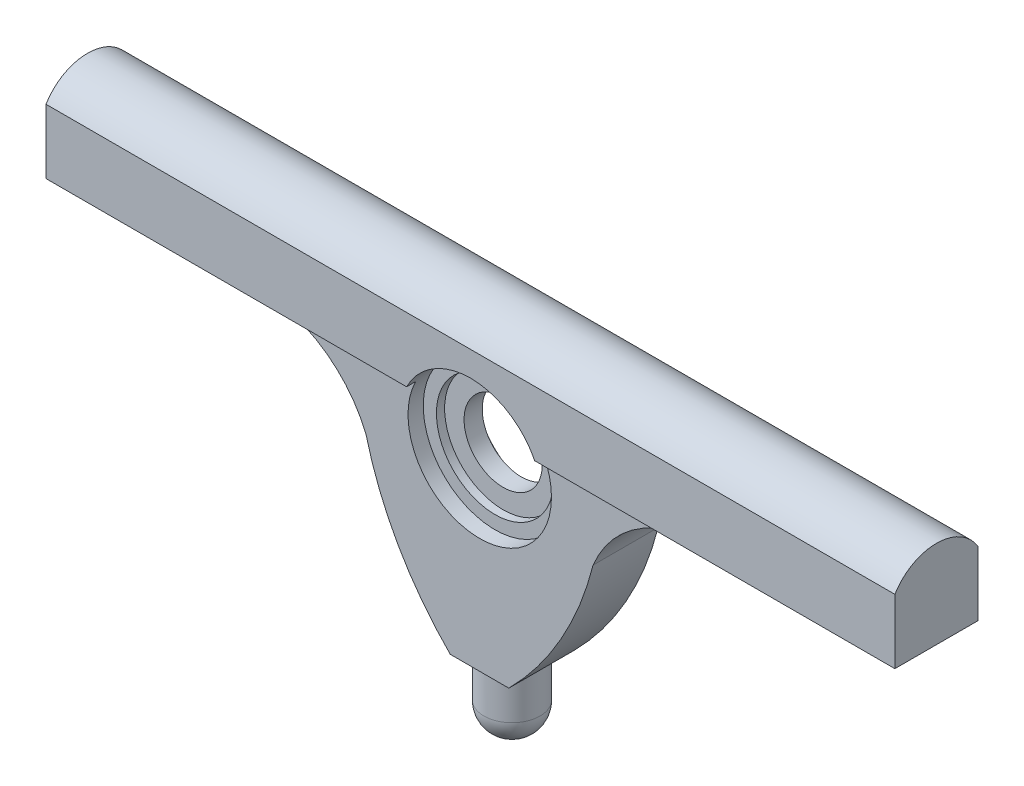
SolidWorks part; units mm, degrees
ref_plane "Front Plane" through (0, 0, 0) normal (0, 0, 1) x (1, 0, 0)
ref_plane "Top Plane" through (0, 0, 0) normal (0, 1, 0) x (1, 0, 0)
ref_plane "Right Plane" through (0, 0, 0) normal (1, 0, 0) x (0, 0, -1)
sketch "Sketch1" plane through (0, 0, 0) normal (1, 0, 0) x (0, 0, -1)
  line L1 (-9.017, -6.985) -> (9.017, -6.985)
  line L2 (-9.017, -6.985) -> (-9.017, 6.985)
  line L4 (9.017, -6.985) -> (9.017, 6.985)
  line L5 (-9.017, -6.985) -> (9.017, 6.985) construction
  line L6 (-9.017, 6.985) -> (9.017, -6.985) construction
  arc A0 (-9.017, 6.985) -> (9.017, 6.985) centre (0, 1.5224) cw
  point P0 (0, 0)
  point P7 (0, 12.065)
  dimension "D1" = 19.05
  dimension "D2" = 13.97
  dimension "D3" = 18.034
extrude "Boss-Extrude1" add sketch "Sketch1" along normal mid plane 184.15
sketch3d "3DSketch1"
  line L0 (0, -6.985, 0) -> (0, -54.483, 0) construction
  line L1 (-24.638, -22.225, 0) -> (0, -22.225, 0) construction
  line L2 (6.35, -54.483, 0) -> (-6.35, -54.483, 0)
  line L3 (-43.18, -6.985, 0) -> (43.18, -6.985, 0)
  arc A0 (-43.18, -6.985, 0) -> (-24.638, -22.225, 0) centre (-48.1235, -31.8993, 0) cw
  arc A1 (-24.638, -22.225, 0) -> (-6.35, -54.483, 0) centre (43.0905, -5.1407, 0) cw
  arc A2 (24.638, -22.225, 0) -> (6.35, -54.483, 0) centre (-43.0905, -5.1407, 0) ccw
  arc A3 (43.18, -6.985, 0) -> (24.638, -22.225, 0) centre (48.1235, -31.8993, 0) ccw
  point P7 (-48.1235, -31.8993, -25.4)
  point P10 (43.0905, -5.1407, 69.85)
  point P15 (-43.0905, -5.1407, -69.85)
  point P18 (48.1235, -31.8993, 25.4)
  dimension "D5" = 25.4
  dimension "D6" = 69.85
  dimension "D1" = 24.638
  dimension "D2" = 47.498
  dimension "D3" = 15.24
  dimension "D4" = 43.18
  dimension "D7" = 6.35
extrude "Boss-Extrude2" add sketch "3DSketch1" along direction (0, 0, -1) on the side of the normal mid plane 14.097
ref_plane "Plane1" through (0, 0, 0) normal (0, 0, 1) x (1, 0, 0)
sketch "Sketch8" plane through (0, 0, 0) normal (0, 0, 1) x (1, 0, 0)
  line L0 (0, -69.469) -> (0, -54.483)
  line L1 (-6.35, -54.483) -> (6.35, -54.483) construction
  line L2 (0, -54.483) -> (6.096, -54.483)
  line L3 (6.096, -54.483) -> (6.096, -63.373)
  line L4 (0, -47.1342) -> (0, -77.1544) construction
  arc A0 (6.096, -63.373) -> (0, -69.469) centre (0, -63.373) cw
  dimension "D1" = 8.89
  dimension "D2" = 6.096
revolve "Revolve2" add sketch "Sketch8" angle 360 about L4
sketch "Sketch9" plane through (0, 0, 7.0485) normal (0, 0, 1) x (1, 0, 0)
  circle A0 centre (0.0506, -13.9773) radius 4.6736
  ellipse E0 centre (9.5866, -13.9773) end of major axis (9.5866, -18.6509) minor radius 4.4873 construction
ref_plane "Plane2" through (0, -13.9773, 0) normal (0, -1, 0) x (-1, 0, 0)
sketch "Sketch10" plane through (0, -13.9773, 0) normal (0, -1, 0) x (-1, 0, 0)
  line L0 (-0.0506, -55.7699) -> (-0.0506, 64.4216) construction
  line L1 (-0.0506, -9.017) -> (-0.0506, 9.017)
  line L2 (19.1976, 0) -> (-22.9025, 0) construction
  line L4 (-0.0506, 9.017) -> (-15.6081, 9.017)
  line L5 (-15.6081, 9.017) -> (-15.6081, 3.7465)
  line L6 (-15.6081, 3.7465) -> (-12.7506, 3.7465)
  line L7 (-12.7506, 3.7465) -> (-12.7506, 1.9685)
  line L8 (-12.7506, 1.9685) -> (-8.5342, 1.9685)
  line L9 (-8.5342, 1.9685) -> (-8.5342, -1.9685)
  line L10 (-64.6711, 0) -> (64.6711, 0) construction
  line L12 (-0.0506, -9.017) -> (-15.6081, -9.017)
  line L13 (-15.6081, -9.017) -> (-15.6081, -3.7465)
  line L14 (-15.6081, -3.7465) -> (-12.7506, -3.7465)
  line L15 (-12.7506, -3.7465) -> (-12.7506, -1.9685)
  line L16 (-12.7506, -1.9685) -> (-8.5342, -1.9685)
  line L17 (-92.075, 9.017) -> (92.075, 9.017) construction
  point P5 (-0.0506, 0)
  point P23 (-8.5342, 0)
  dimension "D3" = 15.5575
  dimension "D4" = 12.7
  dimension "D5" = 8.4836
revolve "Cut-Revolve1" cut sketch "Sketch10" angle 360 about L0
